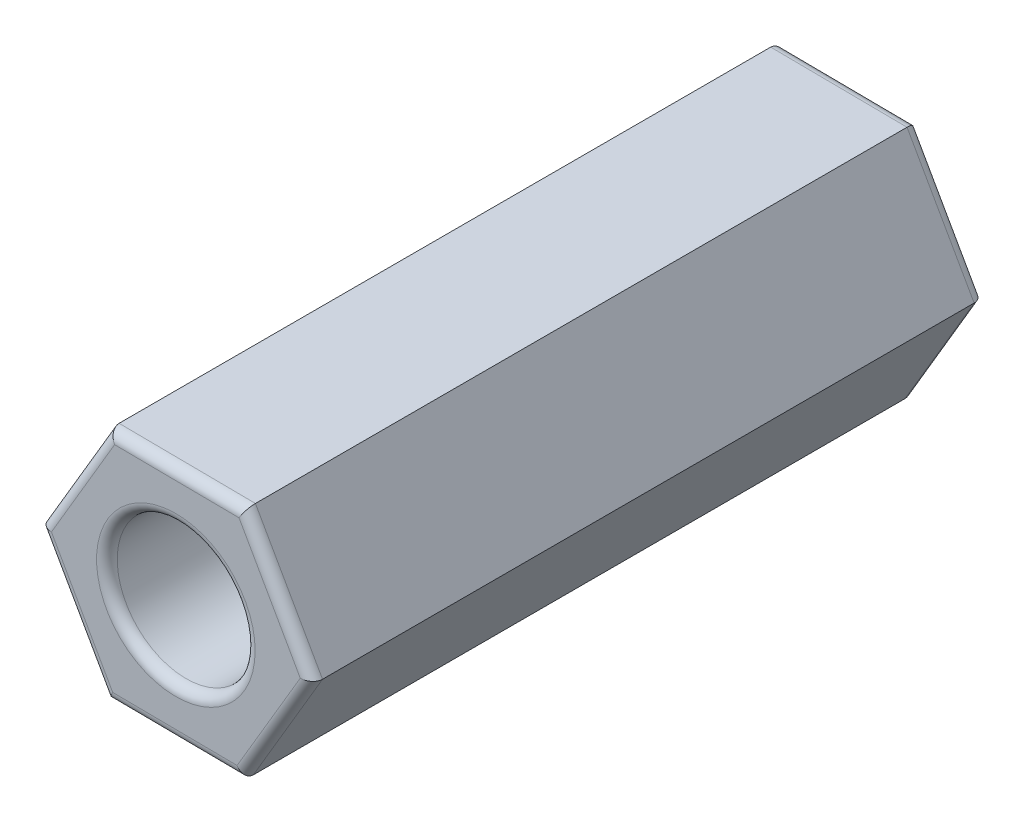
SolidWorks part; units mm, degrees
ref_plane "Спереди" through (0, 0, 0) normal (0, 0, 1) x (1, 0, 0)
ref_plane "Сверху" through (0, 0, 0) normal (0, 1, 0) x (1, 0, 0)
ref_plane "Справа" through (0, 0, 0) normal (1, 0, 0) x (0, 0, -1)
sketch "Эскиз1" plane through (0, 0, 0) normal (0, 0, 1) x (1, 0, 0)
  line L1 (2.0083, 3.407) -> (-1.9464, 3.4427)
  line L2 (-1.9464, 3.4427) -> (-3.9547, 0.0358)
  line L3 (-3.9547, 0.0358) -> (-2.0083, -3.407)
  line L4 (-2.0083, -3.407) -> (1.9464, -3.4427)
  line L5 (1.9464, -3.4427) -> (3.9547, -0.0358)
  line L6 (3.9547, -0.0358) -> (2.0083, 3.407)
  circle A0 centre (0, 0) radius 3.425 construction
  dimension "D1" = 6.85
extrude "Бобышка-Вытянуть1" add sketch "Эскиз1" along normal blind 19.5
sketch "Эскиз2" plane through (0, 0, 19.5) normal (0, 0, 1) x (1, 0, 0)
  line L0 (-1.3229, 1.5) -> (1.3229, 1.5)
  arc A0 (-1.3229, 1.5) -> (1.3229, 1.5) centre (0, 0) ccw
  dimension "D1" = 1.5
  dimension "D2" = 2
extrude "Вырез-Вытянуть1" cut sketch "Эскиз2" against normal blind 12.5
sketch "Эскиз3" plane through (0, 0, 19.5) normal (0, 0, 1) x (1, 0, 0)
  circle A0 centre (0, 0) radius 2
extrude "Вырез-Вытянуть2" cut sketch "Эскиз3" against normal blind 4
fillet "Скругление1" radius 0.3 13 edges at (0.031, 3.4249, 0) (-2.9505, 1.7393, 0) (-2.9815, -1.6856, 0) (-0.031, -3.4249, 0) (2.9505, -1.7393, 0) (2.9815, 1.6856, 0) (2.9505, -1.7393, 19.5) (-0.031, -3.4249, 19.5) (-2.9815, -1.6856, 19.5) (-2.9505, 1.7393, 19.5) (0.031, 3.4249, 19.5) (2.9815, 1.6856, 19.5) (2, 0, 19.5)
fillet "Скругление2" radius 0.2 1 edges at (0, 1.5, 15.5)
